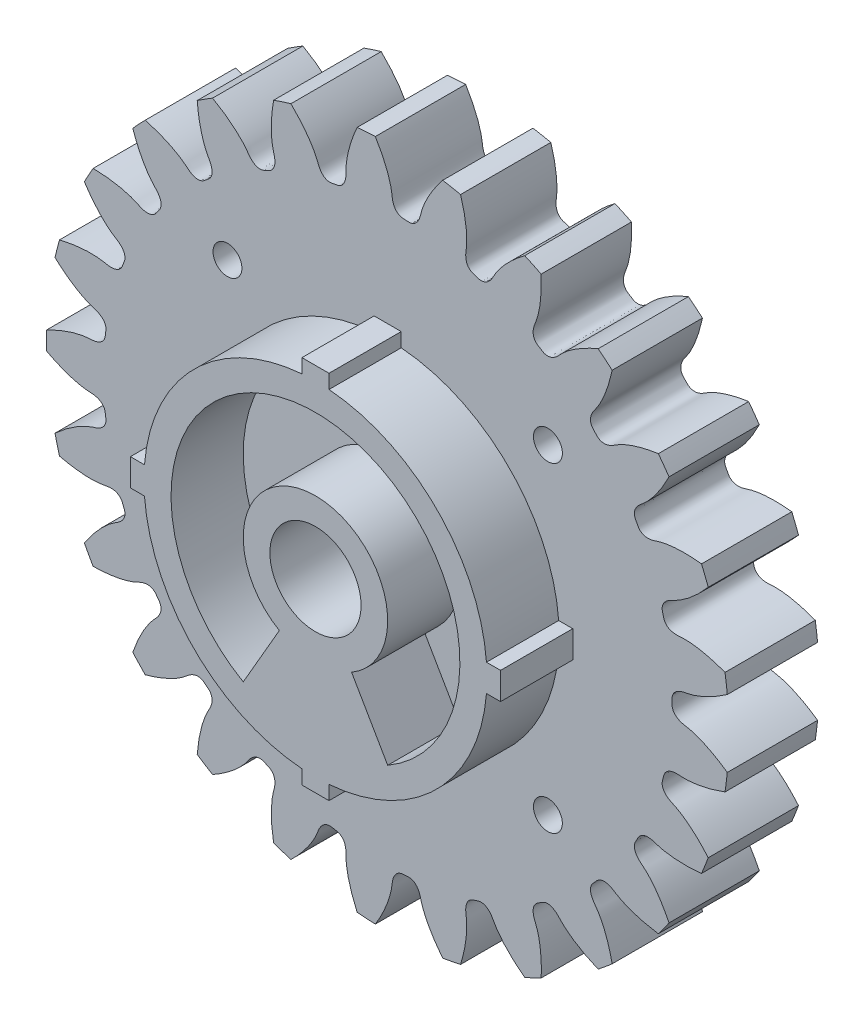
SolidWorks part; units mm, degrees
ref_plane "Front Plane" through (0, 0, 0) normal (0, 0, 1) x (1, 0, 0)
ref_plane "Top Plane" through (0, 0, 0) normal (0, 1, 0) x (1, 0, 0)
ref_plane "Right Plane" through (0, 0, 0) normal (1, 0, 0) x (0, 0, -1)
ref_axis "Axis1" through (0, 0, 55) along (0, 0, -1)
sketch "SketchRevolveSpurGear" plane through (0, 0, 0) normal (1, 0, 0) x (0, 0, -1)
  line L0 (0, 0) -> (1, 0) construction
  line L1 (-5, 0) -> (-5, 37.8)
  line L2 (-5, 37.8) -> (5, 37.8)
  line L3 (5, 37.8) -> (5, 0)
  line L4 (5, 0) -> (-5, 0)
  dimension "Side1" = 5
  dimension "OutsideRadius" = 37.8
  dimension "Side2" = 5
revolve "SpurGear" add sketch "SketchRevolveSpurGear" angle 360 about L0
sketch "SketchToothSpurGear" plane through (0, 0, 0) normal (0, 0, 1) x (1, 0, 0)
  arc A0 (37.7462, 3.8297) -> (37.7462, -3.8297) centre (0, 0) cw
  spline S0 degree 3 poles (37.7462, -3.8297) (37.4665, -3.6288) (37.0499, -3.3463) (36.494, -3.0043) (36.1052, -2.7803) (35.7341, -2.5804) (35.3817, -2.4034) (35.049, -2.2481) (34.7369, -2.1133) (34.4464, -1.9975) (34.1782, -1.8994) (33.9331, -1.8177) (33.7118, -1.7509) (33.515, -1.6976) (33.3431, -1.6562) (33.0382, -1.5923) (32.7367, -1.551) (32.4495, -1.4566) (32.3116, -1.402) (32.1782, -1.3375) (32.0482, -1.2605) (31.9207, -1.1669) (31.7963, -1.0505) (31.679, -0.904) (31.578, -0.7206) (31.5159, -0.5145) (31.4909, -0.2695) (31.5055, 0) (31.4909, 0.2695) (31.5159, 0.5145) (31.578, 0.7206) (31.679, 0.904) (31.7963, 1.0505) (31.9207, 1.1669) (32.0482, 1.2605) (32.1782, 1.3375) (32.3116, 1.402) (32.4495, 1.4566) (32.7367, 1.551) (33.0382, 1.5923) (33.3431, 1.6562) (33.515, 1.6976) (33.7118, 1.7509) (33.9331, 1.8177) (34.1782, 1.8994) (34.4464, 1.9975) (34.7369, 2.1133) (35.049, 2.2481) (35.3817, 2.4034) (35.7341, 2.5804) (36.1052, 2.7803) (36.494, 3.0043) (37.0499, 3.3463) (37.4665, 3.6288) (37.7462, 3.8297) knots 0 0 0 0 0.066628 0.097312 0.126243 0.153421 0.178845 0.202515 0.224432 0.244596 0.263007 0.279664 0.294568 0.307718 0.319115 0.328758 0.367986 0.377666 0.387173 0.396652 0.406297 0.416368 0.427194 0.439149 0.45255 0.467442 0.48044 0.5 0.51956 0.532558 0.54745 0.560851 0.572806 0.583632 0.593703 0.603348 0.612827 0.622334 0.632014 0.671242 0.680885 0.692282 0.705432 0.720336 0.736993 0.755404 0.775568 0.797485 0.821155 0.846579 0.873757 0.902688 0.933372 1 1 1 1
extrude "ToothExtrudeCutSpurGear" cut sketch "SketchToothSpurGear" against normal blind 5 and the other way blind 5
pattern_circular "PatternSpurGear" count 25 over 360 about axis through (0, 0, 55) along (0, 0, -1) of "ToothExtrudeCutSpurGear"
sketch "BoreRevolveSketch" plane through (0, 0, 0) normal (1, 0, 0) x (0, 0, -1)
  line L0 (0, 0) -> (1, 0) construction
  line L1 (-5, 0) -> (5, 0)
sketch "AuxiliarySketchSpurGear" plane through (0, 0, 0) normal (0, 0, 1) x (1, 0, 0)
  circle A0 centre (0, 0) radius 35 construction
  circle A1 centre (0, 0) radius 32.8892 construction
  circle A2 centre (0, 0) radius 33.0598 construction
  circle A3 centre (0, 0) radius 37.8 construction
  circle A4 centre (0, 0) radius 31.5 construction
  dimension "PitchDiameter" = 70
  dimension "BaseDiameter" = 65.7785
  dimension "FormDiameter" = 66.1195
  dimension "MajorDiameter" = 75.6
  dimension "MinorDiameter" = 63
sketch "Sketch5" plane through (0, 0, 5) normal (0, 0, 1) x (1, 0, 0)
  circle A0 centre (17.7484, 17.7484) radius 1.6
extrude "Cut-Extrude2" cut sketch "Sketch5" against normal blind 10
sketch "Sketch6" plane through (0, 0, 5) normal (0, 0, 1) x (1, 0, 0)
  line L0 (0, 0) -> (0, -49.6753) construction
  line L1 (0, 0) -> (-16, -27.7128) construction
  line L2 (0, 0) -> (19.7509, -34.2096) construction
  line L3 (-4, -6.9282) -> (-8, -13.8564)
  line L4 (4, -6.9282) -> (8, -13.8564)
  arc A1 (-4, -6.9282) -> (4, -6.9282) centre (0, 0) cw
  arc A2 (-8, -13.8564) -> (8, -13.8564) centre (0, 0) cw
  circle A3 centre (0, 0) radius 19
  point P12 (0, -19)
extrude "Boss-Extrude1" add sketch "Sketch6" along normal blind 8
pattern_circular "CirPattern3" count 4 over 360 about axis through (0, 0, 13) along (0, 0, -1) of "Cut-Extrude2" reverse direction yes
sketch "Sketch7" plane through (0, 0, 5) normal (0, 0, 1) x (1, 0, 0)
  circle A0 centre (0, 0) radius 5.05
sketch "Sketch8" plane through (0, 0, 5) normal (0, 0, 1) x (1, 0, 0)
  line L0 (0, 0) -> (0, 19) construction
  line L2 (-1.5, 17.5) -> (1.5, 17.5)
  line L3 (-1.5, 17.5) -> (-1.5, 20.5)
  line L4 (-1.5, 20.5) -> (1.5, 20.5)
  line L5 (1.5, 17.5) -> (1.5, 20.5)
  line L6 (-1.5, 17.5) -> (1.5, 20.5) construction
  line L7 (-1.5, 20.5) -> (1.5, 17.5) construction
  circle A0 centre (0, 0) radius 19 construction
extrude "Boss-Extrude2" add sketch "Sketch8" along normal blind 8
pattern_circular "CirPattern4" count 4 over 360 about axis through (0, 0, 13) along (0, 0, 1) of "Boss-Extrude2"
sketch "Sketch9" plane through (0, 0, 13) normal (0, 0, 1) x (1, 0, 0)
  circle A0 centre (0, 0) radius 5.05
extrude "Cut-Extrude5" cut sketch "Sketch9" against normal blind 18
sketch "Sketch10" plane through (0, 0, -5) normal (0, 0, -1) x (-1, 0, 0)
  circle A0 centre (-17.7484, 17.7484) radius 4
extrude "Cut-Extrude6" cut sketch "Sketch10" against normal blind 7
pattern_circular "CirPattern5" count 4 over 360 about axis through (0, 0, 55) along (0, 0, -1) of "Cut-Extrude6"
